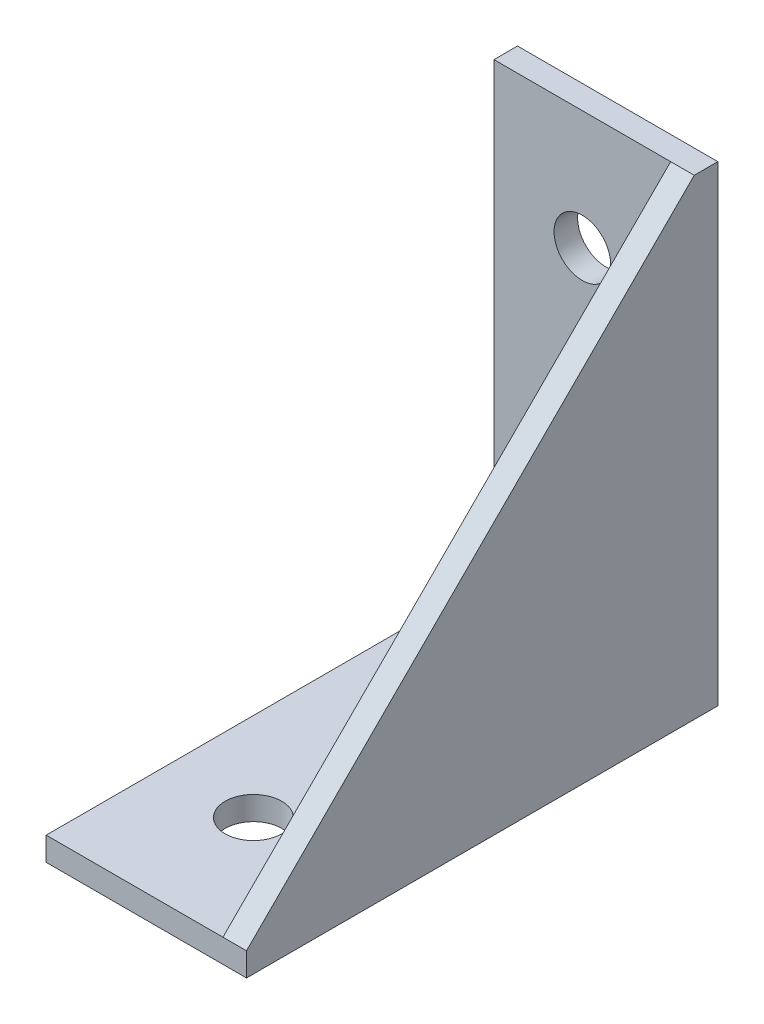
SolidWorks part; units mm, degrees
ref_plane "Front Plane" through (0, 0, 0) normal (0, 0, 1) x (1, 0, 0)
ref_plane "Top Plane" through (0, 0, 0) normal (0, 1, 0) x (1, 0, 0)
ref_plane "Right Plane" through (0, 0, 0) normal (1, 0, 0) x (0, 0, -1)
sketch "Sketch1" plane through (0, 0, 0) normal (1, 0, 0) x (0, 0, -1)
  line L0 (-38, 0) -> (0, 0)
  line L1 (0, 0) -> (0, 38)
  line L2 (0, 38) -> (-38, 0)
  dimension "D1" = 38
extrude "Boss-Extrude1" add sketch "Sketch1" along normal blind 2
sketch "Sketch2" plane through (2, 0, 0) normal (1, 0, 0) x (0, 0, -1)
  line L6 (0, 38) -> (2, 38)
  line L7 (-38, 0) -> (-38, -2)
  line L8 (-38, -2) -> (2, -2)
  line L9 (2, -2) -> (2, 38)
  line L10 (-38, -2) -> (2, -2)
  line L11 (2, -2) -> (2, 38)
  line L12 (0, 38) -> (0, 0)
  line L13 (0, 0) -> (-38, 0)
  dimension "D1" = 2
extrude "Boss-Extrude2" add sketch "Sketch2" against normal blind 17
sketch "Sketch3" plane through (0, 0, 0) normal (0, 1, 0) x (1, 0, 0)
  line L0 (-7.5, 0) -> (-7.5, -38) construction
  line L1 (-15, 0) -> (0, 0) construction
  line L2 (-15, -38) -> (0, -38) construction
  line L3 (-15, -19) -> (0, -19) construction
  line L4 (-15, 0) -> (-15, -38) construction
  line L5 (0, -38) -> (0, 0) construction
  line L6 (-15, 0) -> (0, 0) construction
  circle A0 centre (-7.5, -10.089) radius 2.1
  circle A1 centre (-7.5, -27.911) radius 2.1
  dimension "D1" = 4.2
revolve "Cut-Revolve1" cut sketch "Sketch3" angle 360 about L6
hole_wizard "M4 Clearance Hole1" positions "Sketch6" profile "Sketch7" hole size "M4" standard "ISO" end condition up to next
sketch "Sketch6" plane through (0, 0, 0) normal (0, 0, 1) x (1, 0, 0)
  point P0 (-7.5, 27.911)
  point P2 (-7.5, 10.089)
sketch "Sketch7" plane through (-7.5, 27.911, 0) normal (1, 0, 0) x (0, -1, 0)
  line L0 (0, 0) -> (0, 2)
  line L1 (0, 2) -> (2.4, 2)
  line L2 (2.4, 2) -> (2.4, 0)
  line L5 (2.4, 0) -> (0, 0)
  line L11 (0, -6.35) -> (0, 107.95) construction
  dimension "Thru Hole Dia." = 4.8
  dimension "Thru Hole Depth" = 2
hole_wizard "M4 Clearance Hole2" positions "Sketch8" profile "Sketch9" hole size "M4" standard "ISO" end condition up to next
sketch "Sketch8" plane through (0, 0, 0) normal (0, 1, 0) x (1, 0, 0)
  point P0 (-7.5, -10.089)
  point P2 (-7.5, -27.911)
sketch "Sketch9" plane through (-7.5, 0, 10.089) normal (1, 0, 0) x (0, 0, 1)
  line L0 (0, 0) -> (0, 2)
  line L1 (0, 2) -> (2.4, 2)
  line L2 (2.4, 2) -> (2.4, 0)
  line L5 (2.4, 0) -> (0, 0)
  line L11 (0, -6.35) -> (0, 107.95) construction
  dimension "Thru Hole Dia." = 4.8
  dimension "Thru Hole Depth" = 2
